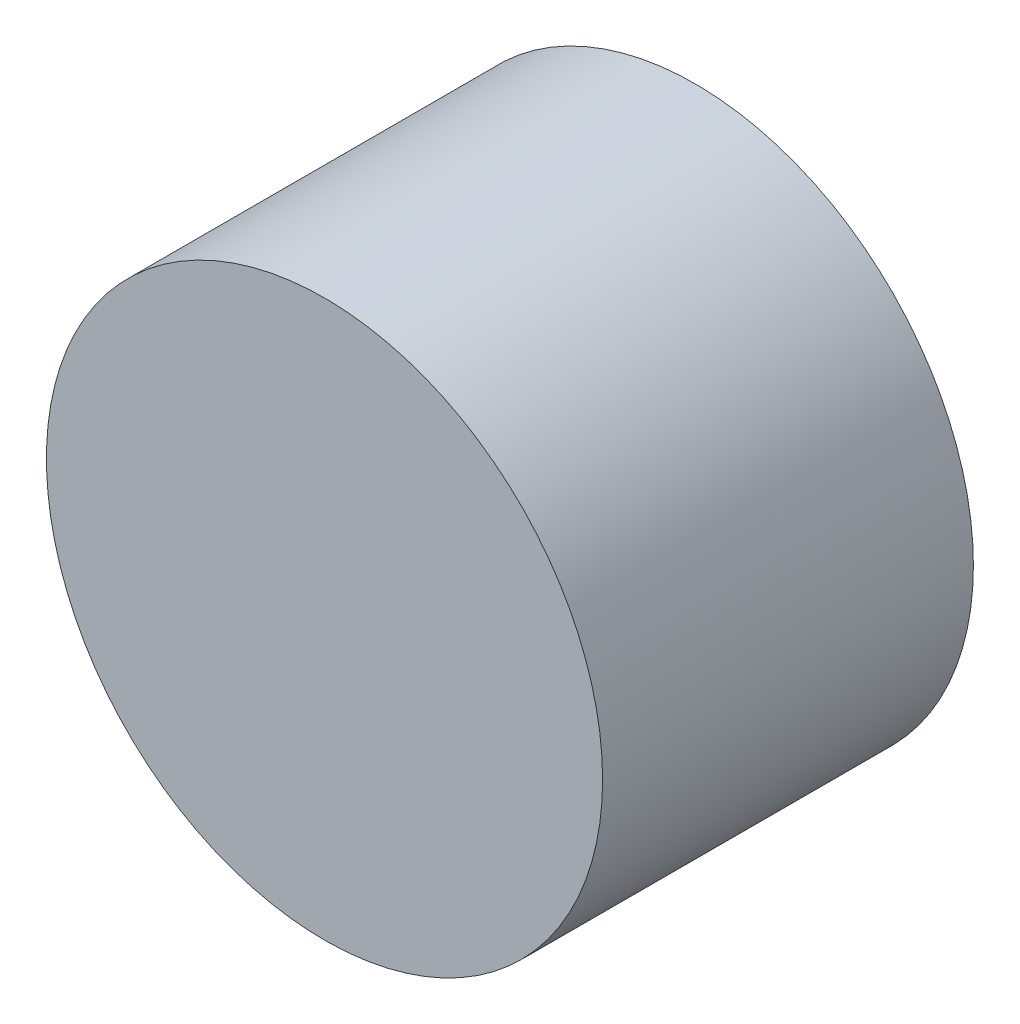
SolidWorks part; units mm, degrees
ref_plane "Front Plane" through (0, 0, 0) normal (0, 0, 1) x (1, 0, 0)
ref_plane "Top Plane" through (0, 0, 0) normal (0, 1, 0) x (1, 0, 0)
ref_plane "Right Plane" through (0, 0, 0) normal (1, 0, 0) x (0, 0, -1)
sketch "Sketch1" plane through (0, 0, 0) normal (0, 0, 1) x (1, 0, 0)
  circle A0 centre (0, 0) radius 6.25
  circle A1 centre (0, 0) radius 7.5
  dimension "D1" = 12.5
  dimension "D2" = 15
extrude "Boss-Extrude1" add sketch "Sketch1" along normal blind 10 contours A1
extrude "Cut-Extrude1" cut sketch "Sketch1<3>" along normal blind 8 contours A0
sketch "Sketch1<3>" plane through (0, 0, 0) normal (0, 0, 1) x (1, 0, 0) same geometry as "Sketch1"
